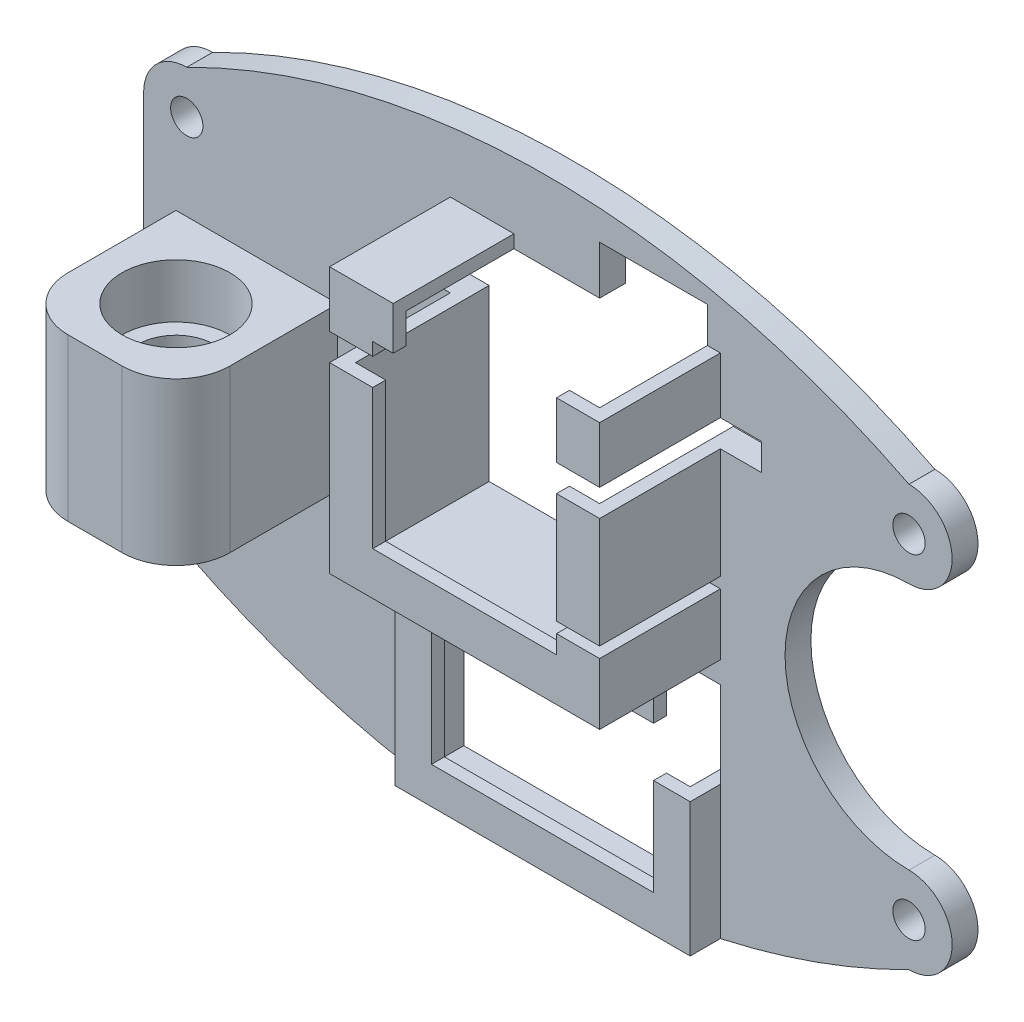
SolidWorks part; units mm, degrees
material "ABS"
ref_plane "Alzado" through (0, 0, 0) normal (0, 0, 1) x (1, 0, 0)
ref_plane "Planta" through (0, 0, 0) normal (0, 1, 0) x (1, 0, 0)
ref_plane "Vista lateral" through (0, 0, 0) normal (1, 0, 0) x (0, 0, -1)
sketch "Croquis1" plane through (0, 0, 0) normal (0, 0, 1) x (1, 0, 0)
  line L0 (-65.9407, 48.6885) -> (-65.9407, 17.6885)
  line L1 (-61.9407, 52.6885) -> (5.0593, 52.6885) construction
  line L2 (-61.9407, 13.6885) -> (5.0593, 13.6885) construction
  line L3 (-28.4407, 52.6885) -> (-28.4407, 60.6885) construction
  line L4 (-28.4407, 13.6885) -> (-28.4407, 5.6885) construction
  circle A0 centre (-61.9407, 48.6885) radius 1.5
  circle A1 centre (5.0593, 48.6885) radius 1.5
  circle A2 centre (5.0593, 17.6885) radius 1.5
  circle A3 centre (-61.9407, 17.6885) radius 1.5
  arc A4 (-61.9407, 52.6885) -> (-65.9407, 48.6885) centre (-61.9407, 48.6885) ccw
  arc A5 (-65.9407, 17.6885) -> (-61.9407, 13.6885) centre (-61.9407, 17.6885) ccw
  arc A6 (-61.9407, 13.6885) -> (5.0593, 13.6885) centre (-28.4407, 79.8291) ccw
  arc A7 (5.0593, 13.6885) -> (5.0593, 21.6885) centre (5.0593, 17.6885) ccw
  arc A8 (5.0593, 44.6885) -> (5.0593, 21.6885) centre (5.0593, 33.1885) ccw
  arc A9 (5.0593, 44.6885) -> (5.0593, 52.6885) centre (5.0593, 48.6885) ccw
  arc A10 (5.0593, 52.6885) -> (-61.9407, 52.6885) centre (-28.4407, -13.4521) ccw
  dimension "D2" = 8
  dimension "D3" = 8
  dimension "D5" = 4
  dimension "D6" = 4
  dimension "D7" = 3
  dimension "D8" = 3
  dimension "D9" = 4
  dimension "D10" = 3
  dimension "D11" = 4
  dimension "D12" = 3
  dimension "D13" = 11.5
  dimension "D1" = 67
  dimension "D4" = 31
extrude "Saliente-Extruir1" add sketch "Croquis1" along normal blind 2.4
sketch "Croquis3" plane through (0, 0, 2.4) normal (0, 0, 1) x (1, 0, 0)
  line L0 (-12.4407, 54.4855) -> (-12.4407, 29.8355)
  line L1 (-36.2907, 53.2855) -> (-13.6407, 53.2855)
  line L2 (-36.2907, 53.2855) -> (-36.2907, 31.0355)
  line L3 (-36.2907, 31.0355) -> (-13.6407, 31.0355)
  line L4 (-13.6407, 53.2855) -> (-13.6407, 31.0355)
  line L5 (-37.4907, 29.8355) -> (-12.4407, 29.8355)
  line L6 (-37.4907, 54.4855) -> (-37.4907, 29.8355)
  line L7 (-37.4907, 54.4855) -> (-12.4407, 54.4855)
  line L8 (-39.8407, 27.8355) -> (-39.8407, 7.4355) construction
  line L9 (-38.6407, 26.6355) -> (-13.6407, 26.6355) construction
  line L10 (-38.6407, 26.6355) -> (-38.6407, 8.6355) construction
  line L11 (-38.6407, 8.6355) -> (-13.6407, 8.6355) construction
  line L12 (-13.6407, 26.6355) -> (-13.6407, 8.6355) construction
  line L13 (-39.8407, 7.4355) -> (-12.4407, 7.4355) construction
  line L14 (-12.4407, 27.8355) -> (-12.4407, 7.4355) construction
  line L15 (-39.8407, 27.8355) -> (-12.4407, 27.8355) construction
  line L16 (-6.4407, 33.1885) -> (-12.4407, 33.1885) construction
  arc A0 (5.0593, 44.6885) -> (5.0593, 21.6885) centre (5.0593, 33.1885) ccw construction
  arc A1 (-61.9407, 13.6885) -> (5.0593, 13.6885) centre (-28.4407, 79.8291) ccw construction
  dimension "D1" = 22.65
  dimension "D2" = 22.25
  dimension "D4" = 18
  dimension "D5" = 25
  dimension "D7" = 6
  dimension "D8" = 2
  dimension "D3" = 1.2
  dimension "D6" = 1.2
extrude "Saliente-Extruir2" add sketch "Croquis3" along normal blind 10
sketch "Croquis4" plane through (0, 0, 12.4) normal (0, 0, 1) x (1, 0, 0)
  line L0 (-33.4907, 50.4855) -> (-33.4907, 33.8355)
  line L1 (-37.4907, 54.4855) -> (-12.4407, 54.4855)
  line L2 (-37.4907, 54.4855) -> (-37.4907, 29.8355)
  line L3 (-37.4907, 29.8355) -> (-12.4407, 29.8355)
  line L4 (-12.4407, 54.4855) -> (-12.4407, 29.8355)
  line L5 (-33.4907, 33.8355) -> (-16.4407, 33.8355)
  line L6 (-16.4407, 50.4855) -> (-16.4407, 33.8355)
  line L7 (-33.4907, 50.4855) -> (-16.4407, 50.4855)
  dimension "D1" = 4
extrude "Saliente-Extruir3" add sketch "Croquis4" along normal blind 1.2
sketch "Croquis5" plane through (0, 0, 13.6) normal (0, 0, 1) x (1, 0, 0)
  line L0 (-33.4907, 50.4855) -> (-33.4907, 33.8355) construction
  line L1 (-33.4907, 49.2855) -> (-37.4907, 49.2855)
  line L2 (-33.4907, 49.2855) -> (-33.4907, 46.7855)
  line L3 (-33.4907, 46.7855) -> (-37.4907, 46.7855)
  line L4 (-37.4907, 49.2855) -> (-37.4907, 46.7855)
  line L5 (-37.4907, 54.4855) -> (-37.4907, 29.8355) construction
  line L6 (-12.4407, 54.4855) -> (-37.4907, 54.4855) construction
  line L7 (-16.4407, 50.4855) -> (-31.5907, 50.4855)
  line L8 (-16.4407, 50.4855) -> (-16.4407, 54.4855)
  line L9 (-16.4407, 54.4855) -> (-31.5907, 54.4855)
  line L10 (-31.5907, 50.4855) -> (-31.5907, 54.4855)
  line L11 (-16.4407, 50.4855) -> (-33.4907, 50.4855) construction
  line L12 (-16.4407, 33.8355) -> (-16.4407, 50.4855) construction
  line L17 (-12.4407, 29.8355) -> (-12.4407, 54.4855) construction
  line L19 (-16.4407, 35.5355) -> (-12.4407, 35.5355)
  line L20 (-16.4407, 35.5355) -> (-16.4407, 36.5355)
  line L21 (-16.4407, 36.5355) -> (-12.4407, 36.5355)
  line L22 (-12.4407, 35.5355) -> (-12.4407, 36.5355)
  line L23 (-37.4907, 29.8355) -> (-12.4407, 29.8355) construction
  line L24 (-24.9657, 33.8355) -> (-24.9657, 50.4855) construction
  line L25 (-33.4907, 33.8355) -> (-16.4407, 33.8355) construction
  line L26 (-12.4407, 49.2855) -> (-12.4407, 46.7855)
  line L27 (-16.4407, 46.7855) -> (-12.4407, 46.7855)
  line L28 (-16.4407, 49.2855) -> (-16.4407, 46.7855)
  line L29 (-16.4407, 49.2855) -> (-12.4407, 49.2855)
  dimension "D1" = 5.2
  dimension "D2" = 2.5
  dimension "D3" = 15.15
  dimension "D4" = 5.7
  dimension "D5" = 1
extrude "Cortar-Extruir1" cut sketch "Croquis5" against normal up to vertex (11.2 mm away) up to point (-37.4907, 29.8355, 2.4)
sketch "Croquis6" plane through (0, 0, 2.4) normal (0, 0, 1) x (1, 0, 0)
  line L1 (-39.8407, 27.8355) -> (-12.4407, 27.8355)
  line L2 (-39.8407, 27.8355) -> (-39.8407, 7.4355)
  line L3 (-39.8407, 7.4355) -> (-12.4407, 7.4355)
  line L4 (-12.4407, 27.8355) -> (-12.4407, 7.4355)
  line L5 (-38.6407, 26.6355) -> (-13.6407, 26.6355)
  line L6 (-38.6407, 26.6355) -> (-38.6407, 8.6355)
  line L7 (-38.6407, 8.6355) -> (-13.6407, 8.6355)
  line L8 (-13.6407, 26.6355) -> (-13.6407, 8.6355)
extrude "Saliente-Extruir4" add sketch "Croquis6" along normal blind 1.6
sketch "Croquis8" plane through (0, 0, 2.4) normal (0, 0, 1) x (1, 0, 0)
  line L0 (-6.4407, 33.1885) -> (-65.9407, 33.1885) construction
  line L1 (-65.9407, 48.6885) -> (-65.9407, 17.6885) construction
  line L3 (-62.9407, 40.6885) -> (-47.9407, 40.6885)
  line L4 (-62.9407, 40.6885) -> (-62.9407, 25.6885)
  line L5 (-62.9407, 25.6885) -> (-47.9407, 25.6885)
  line L6 (-47.9407, 40.6885) -> (-47.9407, 25.6885)
  arc A0 (5.0593, 44.6885) -> (5.0593, 21.6885) centre (5.0593, 33.1885) ccw construction
  point P11 (-47.9407, 33.1885)
  dimension "D1" = 15
  dimension "D2" = 15
  dimension "D3" = 3
extrude "Saliente-Extruir5" add sketch "Croquis8" along normal blind 15
sketch "Croquis10" plane through (0, 25.6885, 0) normal (0, -1, 0) x (1, 0, 0)
  line L0 (-62.9407, 2.4) -> (-47.9407, 2.4) construction
  line L1 (-62.9407, 17.4) -> (-47.9407, 17.4) construction
  circle A0 centre (-55.4407, 9.9) radius 5
  point P4 (0, 0)
  point P7 (-55.4407, 17.4)
  dimension "D1" = 10
  dimension "D2" = 7.5
extrude "Cortar-Extruir2" cut sketch "Croquis10" against normal blind 5
extrude "Cortar-Extruir3" cut sketch "Croquis10<2>" along normal blind 5 from surface starting at face at (-55.4407, 40.6885, 9.9)
sketch "Croquis10<2>" plane through (0, 25.6885, 0) normal (0, -1, 0) x (1, 0, 0) same geometry as "Croquis10"
sketch "Croquis11" plane through (0, 30.6885, 0) normal (0, -1, 0) x (1, 0, 0)
  circle A0 centre (-55.4407, 9.9) radius 3.5
  dimension "D1" = 7
extrude "Cortar-Extruir4" cut sketch "Croquis11" against normal up to surface (5 mm away) up to face at (-50.4407, 35.6885, 9.9)
sketch "Croquis12" plane through (0, 0, 2.4) normal (0, 0, 1) x (1, 0, 0)
  line L0 (-24.9657, 53.2855) -> (-24.9657, 31.0355) construction
  line L1 (-36.2907, 53.2855) -> (-13.6407, 53.2855)
  line L2 (-36.2907, 53.2855) -> (-36.2907, 49.2855)
  line L3 (-36.2907, 31.0355) -> (-13.6407, 31.0355)
  line L5 (-36.2907, 49.2855) -> (-41.2907, 49.2855)
  line L7 (-36.2907, 46.7855) -> (-41.2907, 46.7855)
  line L8 (-41.2907, 49.2855) -> (-41.2907, 46.7855)
  line L9 (-36.2907, 46.7855) -> (-36.2907, 31.0355)
  line L10 (-13.6407, 46.7855) -> (-13.6407, 31.0355)
  line L11 (-8.6407, 49.2855) -> (-8.6407, 46.7855)
  line L12 (-13.6407, 46.7855) -> (-8.6407, 46.7855)
  line L13 (-13.6407, 49.2855) -> (-8.6407, 49.2855)
  line L14 (-13.6407, 53.2855) -> (-13.6407, 49.2855)
  line L15 (-37.4907, 46.7855) -> (-36.2907, 46.7855) construction
  dimension "D1" = 5
extrude "Cortar-Extruir5" cut sketch "Croquis12" against normal up to vertex (2.4 mm away) up to point (5.0593, 52.6885, 0)
sketch "Croquis13" plane through (0, 0, 2.4) normal (0, 0, 1) x (1, 0, 0)
  line L0 (-12.4407, 49.2855) -> (-12.4407, 54.4855) construction
  line L1 (-23.6407, 57.7855) -> (-13.6407, 57.7855)
  line L2 (-23.6407, 57.7855) -> (-23.6407, 53.2855)
  line L3 (-23.6407, 53.2855) -> (-13.6407, 53.2855)
  line L4 (-13.6407, 57.7855) -> (-13.6407, 53.2855)
  line L5 (-16.4407, 53.2855) -> (-31.5907, 53.2855) construction
  point P4 (-13.6407, 53.265)
  point P7 (-23.6407, 53.2855)
  dimension "D1" = 1.2
  dimension "D2" = 4.5
  dimension "D3" = 10
extrude "Cortar-Extruir6" cut sketch "Croquis13" along normal blind 10 and the other way up to vertex (2.4 mm away) other way up to point (5.0593, 52.6885, 0)
sketch "Croquis14" plane through (0, 0, 4) normal (0, 0, 1) x (1, 0, 0)
  line L0 (-36.4407, 24.4355) -> (-36.4407, 10.8355)
  line L1 (-39.8407, 27.8355) -> (-12.4407, 27.8355)
  line L2 (-39.8407, 27.8355) -> (-39.8407, 7.4355)
  line L3 (-39.8407, 7.4355) -> (-12.4407, 7.4355)
  line L4 (-12.4407, 27.8355) -> (-12.4407, 7.4355)
  line L5 (-36.4407, 10.8355) -> (-15.8407, 10.8355)
  line L6 (-15.8407, 24.4355) -> (-15.8407, 10.8355)
  line L7 (-36.4407, 24.4355) -> (-15.8407, 24.4355)
  dimension "D1" = 3.4
extrude "Saliente-Extruir6" add sketch "Croquis14" along normal blind 1.2
sketch "Croquis15" plane through (0, 0, 2.4) normal (0, 0, 1) x (1, 0, 0)
  line L1 (-38.6407, 26.6355) -> (-13.6407, 26.6355)
  line L2 (-38.6407, 26.6355) -> (-38.6407, 8.6355)
  line L3 (-38.6407, 8.6355) -> (-13.6407, 8.6355)
  line L4 (-13.6407, 26.6355) -> (-13.6407, 8.6355)
extrude "Cortar-Extruir7" cut sketch "Croquis15" against normal up to vertex (2.4 mm away) up to point (-65.9407, 17.6885, 0)
sketch "Croquis16" plane through (0, 0, 5.2) normal (0, 0, 1) x (1, 0, 0)
  line L0 (-12.4407, 27.8355) -> (-39.8407, 27.8355) construction
  line L1 (-15.8407, 27.8355) -> (-12.4407, 27.8355)
  line L2 (-15.8407, 27.8355) -> (-15.8407, 19.8355)
  line L3 (-15.8407, 19.8355) -> (-12.4407, 19.8355)
  line L4 (-12.4407, 27.8355) -> (-12.4407, 19.8355)
  line L5 (-12.4407, 7.4355) -> (-12.4407, 27.8355) construction
  line L6 (-15.8407, 10.8355) -> (-15.8407, 24.4355) construction
  dimension "D1" = 8
extrude "Cortar-Extruir8" cut sketch "Croquis16" against normal up to vertex (5.2 mm away) up to point (5.0593, 13.6885, 0)
fillet "Redondeo1" radius 5 2 edges at (-47.9407, 33.1885, 17.4) (-62.9407, 33.1885, 17.4)
